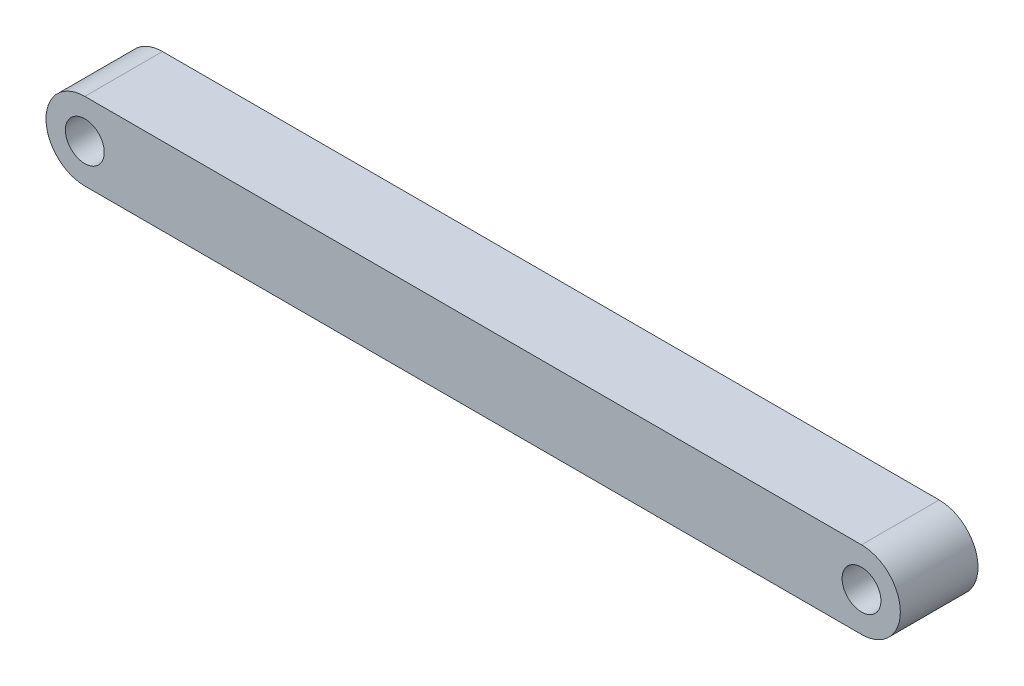
SolidWorks part; units mm, degrees
ref_plane "Plan de face" through (0, 0, 0) normal (0, 0, 1) x (1, 0, 0)
ref_plane "Plan de dessus" through (0, 0, 0) normal (0, 1, 0) x (1, 0, 0)
ref_plane "Plan de droite" through (0, 0, 0) normal (1, 0, 0) x (0, 0, -1)
sketch "Esquisse1" plane through (0, 0, 0) normal (0, 0, 1) x (1, 0, 0)
  line L0 (0, 0) -> (60, 0) construction
  line L1 (0, 3) -> (60, 3)
  line L2 (0, -3) -> (60, -3)
  arc A0 (0, 3) -> (0, -3) centre (0, 0) ccw
  arc A1 (60, -3) -> (60, 3) centre (60, 0) ccw
  circle A2 centre (0, 0) radius 1.5
  circle A3 centre (60, 0) radius 1.5
  point P3 (30, 0)
  dimension "D1" = 3
  dimension "D2" = 6
  dimension "D3" = 60
extrude "Boss.-Extru.1" add sketch "Esquisse1" along normal blind 3 and the other way blind 3
